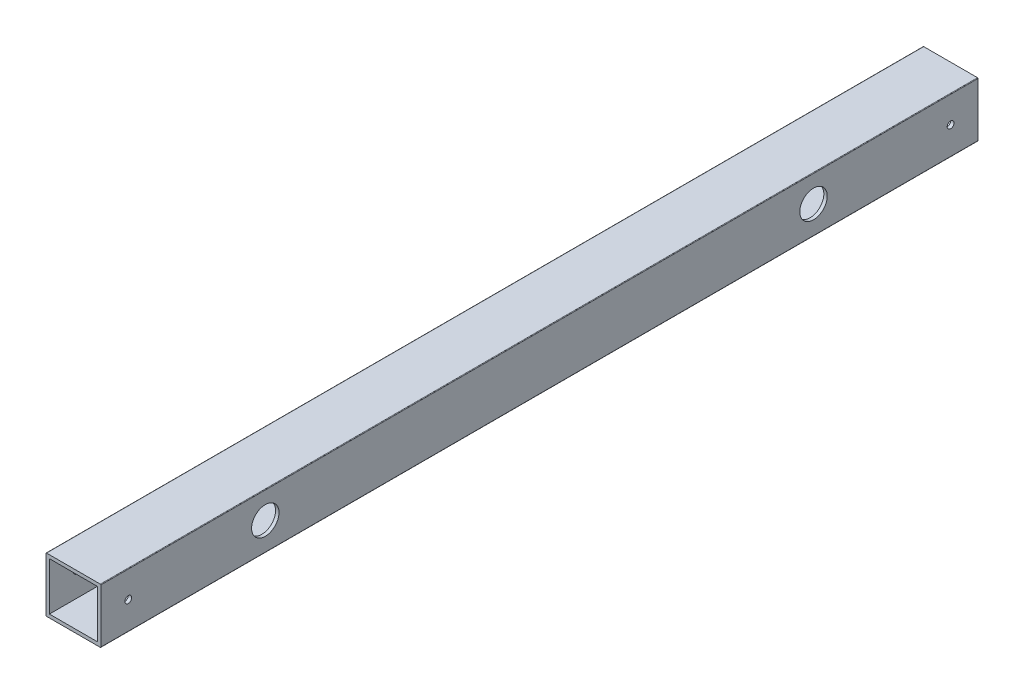
SolidWorks part; units mm, degrees
material "1060 Alloy"
ref_plane "Front Plane" through (0, 0, 0) normal (0, 0, 1) x (1, 0, 0)
ref_plane "Top Plane" through (0, 0, 0) normal (0, 1, 0) x (1, 0, 0)
ref_plane "Right Plane" through (0, 0, 0) normal (1, 0, 0) x (0, 0, -1)
ref_plane "Plane1" through (0, 0, 0) normal (0, 0, -1) x (-1, 0, 0)
sketch "Sketch1" plane through (0, 0, 0) normal (0, 0, -1) x (-1, 0, 0)
  line L4 (1.5875, -1.3335) -> (1.5875, 23.5585)
  line L5 (1.3335, 23.8125) -> (-23.5585, 23.8125)
  line L6 (-23.8125, 23.5585) -> (-23.8125, -1.3335)
  line L7 (-23.5585, -1.5875) -> (1.3335, -1.5875)
  line L9 (0, 22.225) -> (-22.225, 22.225)
  line L10 (0, 22.225) -> (0, 0)
  line L11 (0, 0) -> (-22.225, 0)
  line L12 (-22.225, 22.225) -> (-22.225, 0)
  line L13 (0, 22.225) -> (-22.225, 0) construction
  line L14 (0, 0) -> (-22.225, 22.225) construction
  arc A4 (1.3335, -1.5875) -> (1.5875, -1.3335) centre (1.3335, -1.3335) ccw
  arc A5 (1.5875, 23.5585) -> (1.3335, 23.8125) centre (1.3335, 23.5585) ccw
  arc A6 (-23.5585, 23.8125) -> (-23.8125, 23.5585) centre (-23.5585, 23.5585) ccw
  arc A7 (-23.8125, -1.3335) -> (-23.5585, -1.5875) centre (-23.5585, -1.3335) ccw
  point P24 (-11.1125, 11.1125)
  dimension "D1" = 25.4
  dimension "D2" = 25.4
  dimension "D3" = 1.5875
  dimension "D4" = 1.5875
  dimension "D5" = 1.5875
extrude "Boss-Extrude1" add sketch "Sketch1" against normal blind 406.4
sketch "Sketch2" plane through (-1.5875, 0, 0) normal (-1, 0, 0) x (0, 0, 1)
  line L0 (0, -1.3335) -> (0, 23.5585) construction
  line L1 (406.4, -1.3335) -> (0, -1.3335) construction
  line L2 (406.4, -1.3335) -> (406.4, 23.5585) construction
  circle A0 centre (12.6975, 11.3665) radius 1.5875
  circle A1 centre (393.7, 11.3665) radius 1.5875
  circle A2 centre (76.2, 11.3665) radius 6.35
  circle A3 centre (330.2, 11.3665) radius 6.35
  point P4 (0, 11.1125)
  dimension "D1" = 3.175
  dimension "D2" = 12.7
  dimension "D3" = 12.7
  dimension "D4" = 3.175
  dimension "D5" = 12.7
  dimension "D6" = 12.7
  dimension "D7" = 12.7
  dimension "D8" = 12.7
  dimension "D9" = 76.2
  dimension "D10" = 12.7
  dimension "D11" = 12.7
  dimension "D12" = 76.2
extrude "Cut-Extrude1" cut sketch "Sketch2" against normal through all
